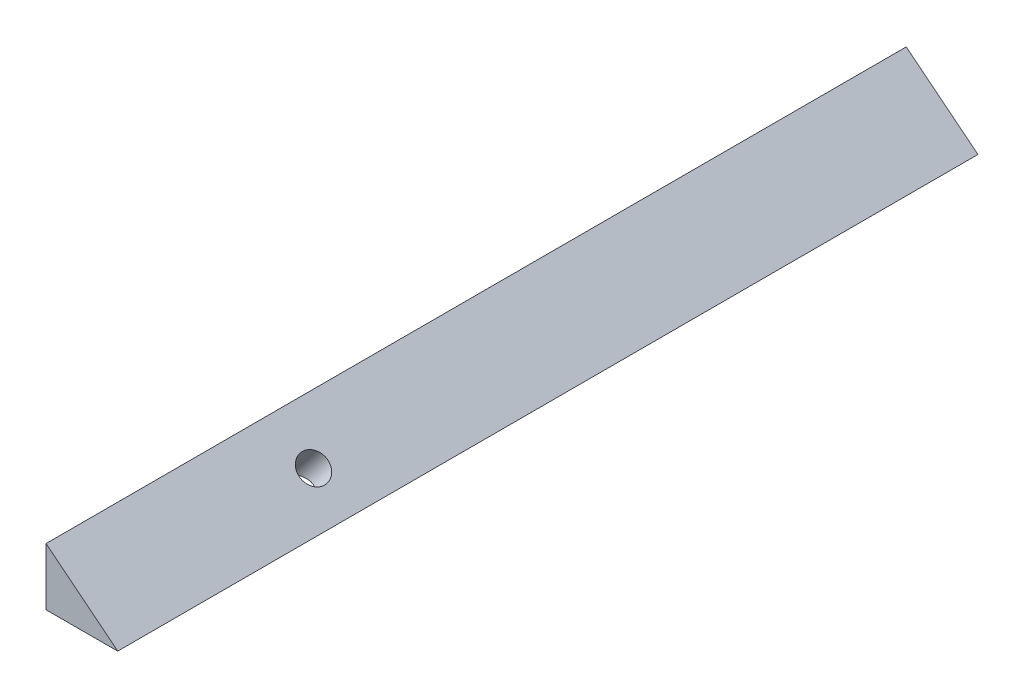
SolidWorks part; units mm, degrees
ref_plane "Front Plane" through (0, 0, 0) normal (0, 0, 1) x (1, 0, 0)
ref_plane "Top Plane" through (0, 0, 0) normal (0, 1, 0) x (1, 0, 0)
ref_plane "Right Plane" through (0, 0, 0) normal (1, 0, 0) x (0, 0, -1)
sketch "Sketch1" plane through (0, 0, 0) normal (0, 0, 1) x (1, 0, 0)
  line L0 (63.5, 0) -> (0, 50.8)
  line L1 (0, 0) -> (63.5, 0)
  line L2 (0, 0) -> (0, 50.8)
  line L3 (0, 50.8) -> (63.5, 50.8)
  line L4 (63.5, 0) -> (63.5, 50.8)
  dimension "D1" = 50.8
  dimension "D2" = 63.5
extrude "Boss-Extrude1" add sketch "Sketch1" against normal blind 38.1 contours L2 L1 L0 region at (21.1667, 16.9333, 0)
sketch "Sketch3" plane through (0, 0, 0) normal (0, 0, 1) x (1, 0, 0)
  line L0 (0, 50.8) -> (0, 0)
  line L1 (0, 0) -> (63.5, 0)
  line L2 (63.5, 0) -> (0, 50.8)
extrude "Boss-Extrude2" add sketch "Sketch3" along normal blind 292.1
sketch "Sketch4" plane through (0, 0, -38.1) normal (0, 0, -1) x (-1, 0, 0)
  line L0 (0, 50.8) -> (-63.5, 0)
  line L1 (-63.5, 0) -> (0, 0)
  line L2 (0, 0) -> (0, 50.8)
extrude "Boss-Extrude3" add sketch "Sketch4" along normal blind 431.8
sketch "Sketch6" plane through (24.7805, 30.9756, 0) normal (0.6247, 0.7809, 0) x (0.7809, -0.6247, 0)
  line L0 (49.5852, 469.9) -> (49.5852, -292.1) construction
  line L1 (49.5852, -292.1) -> (-31.7345, -292.1) construction
  circle A0 centre (11.4852, -88.9) radius 12.7
  dimension "D1" = 25.4
  dimension "D3" = 203.2
  dimension "D2" = 38.1
extrude "Cut-Extrude2" cut sketch "Sketch6" against normal blind 431.8
